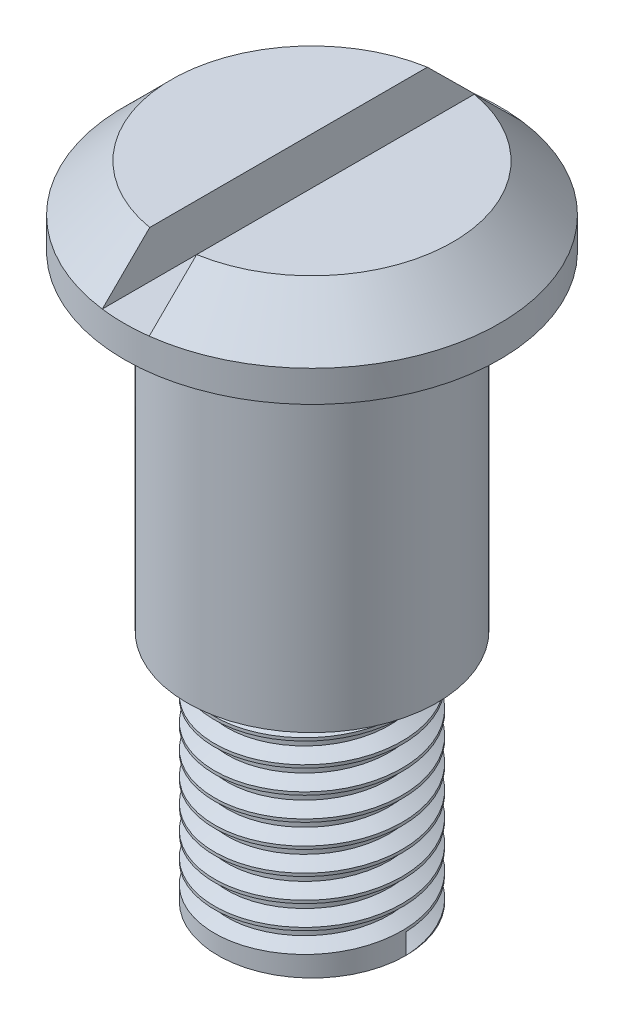
SolidWorks part; units mm, degrees
material "AISI 304"
ref_plane "Front Plane" through (0, 0, 0) normal (0, 0, 1) x (1, 0, 0)
ref_plane "Top Plane" through (0, 0, 0) normal (0, 1, 0) x (1, 0, 0)
ref_plane "Right Plane" through (0, 0, 0) normal (1, 0, 0) x (0, 0, -1)
sketch "Sketch1" plane through (0, 0, 0) normal (1, 0, 0) x (0, 0, -1)
  line L0 (0, 60.8865) -> (0, -56.9808) construction
  line L1 (0, 1.9529) -> (-6, 1.9529)
  line L2 (-6, 1.9529) -> (-6, 16.9529)
  line L3 (-6, 16.9529) -> (-8, 16.9529)
  line L4 (-8, 16.9529) -> (-8, 37.9529)
  line L5 (-8, 37.9529) -> (-12, 37.9529)
  line L6 (-12, 37.9529) -> (-12, 39.9529)
  line L7 (-9, 42.9529) -> (0, 42.9529)
  line L8 (-12, 39.9529) -> (0, 39.9529)
  line L9 (-12, 39.9529) -> (-9, 42.9529)
  point P9 (-12, 42.9529)
  dimension "D1" = 36
  dimension "D2" = 15
  dimension "D3" = 2
  dimension "D4" = 8
  dimension "D5" = 6
  dimension "D6" = 12
  dimension "D7" = 3
  dimension "D8" = 45
revolve "Revolve1" add sketch "Sketch1" angle 360 about L0 region at (0, 41.3814, 5.2857) region at (0, 22.6869, 3.8511)
sketch "Sketch2" plane through (0, 42.9529, 0) normal (0, 1, 0) x (1, 0, 0)
  circle A0 centre (0, 0) radius 1.5
  dimension "D1" = 3
extrude "Cut-Extrude1" cut sketch "Sketch2" against normal blind 3
thread "Thread1" pitch 1.5 method cut profile "Thread Profile1" start angle 0, offset 0, length 15, pitch 1.5, diameter 12
ref_plane "Plane1" through (6, 1.9529, 0) normal (0, 0, 1) x (1, 0, 0)
sketch "Thread Profile1" plane through (6, 1.9529, 0) normal (0, 0, 1) x (1, 0, 0)
  line L0 (0, 0) -> (0, 1.5) construction
  line L11 (0, 0) -> (0, 1.3125)
  line L12 (0, 1.3125) -> (-0.8119, 0.8437)
  line L13 (-0.8119, 0.8437) -> (-0.8119, 0.4687)
  line L15 (-0.8119, 0.4687) -> (0, 0)
  line L17 (-0.8119, 0.6562) -> (0, 0.6562) construction
  point P2 (0, 0)
  dimension "Pitch" = 1.5
  dimension "Profile_Angle" = 60
  dimension "Profile_Land" = 0.375
  dimension "Profile_Height" = 0.8119
sketch "Sketch3" plane through (0, 0, 0) normal (0, 0, 1) x (1, 0, 0)
  line L0 (-1.5, 42.9529) -> (-1.5, 39.9529)
  line L1 (9, 42.9529) -> (-9, 42.9529) construction
  line L2 (-1.5, 39.9529) -> (1.5, 39.9529)
  line L3 (1.5, 39.9529) -> (1.5, 42.9529)
  line L4 (0, 39.9529) -> (0, 42.9529) construction
  line L5 (-1.5, 42.9529) -> (1.5, 42.9529)
  point P4 (0, 39.9529)
  dimension "D1" = 3
  dimension "D2" = 3
extrude "Cut-Extrude2" cut sketch "Sketch3" against normal through all both and the other way through all
